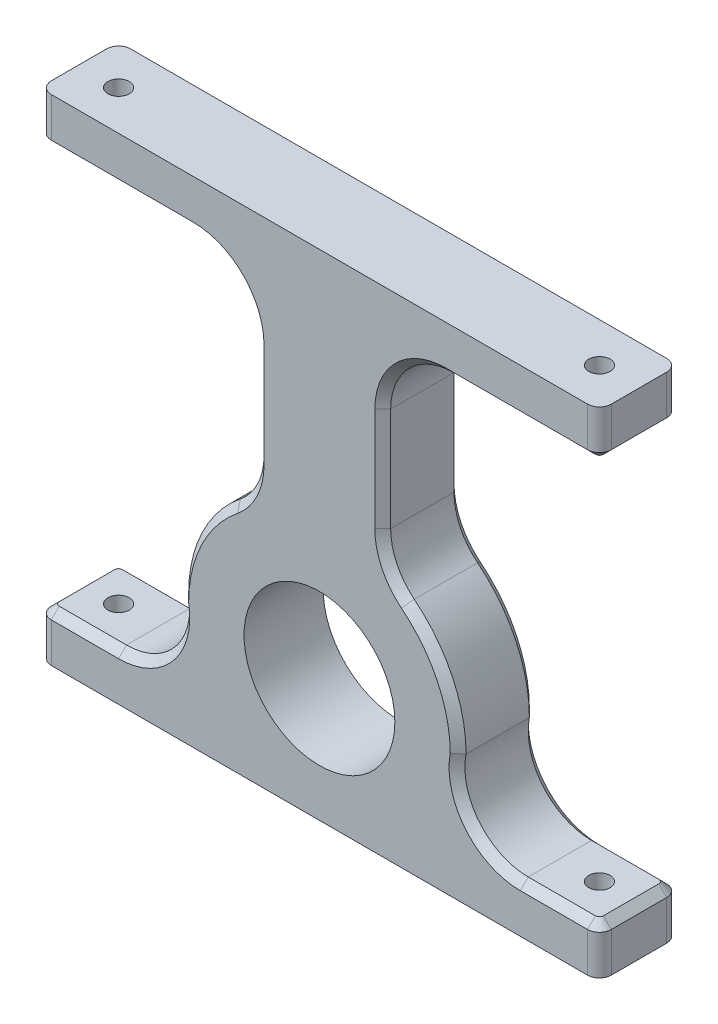
SolidWorks part; units mm, degrees
material "Nylon 101"
ref_plane "Front Plane" through (0, 0, 0) normal (0, 0, 1) x (1, 0, 0)
ref_plane "Top Plane" through (0, 0, 0) normal (0, 1, 0) x (1, 0, 0)
ref_plane "Right Plane" through (0, 0, 0) normal (1, 0, 0) x (0, 0, -1)
sketch "Sketch1" plane through (0, 0, 0) normal (0, 0, 1) x (1, 0, 0)
  line L0 (0, -19.0627) -> (50.7668, -19.0627) construction
  line L1 (50.7668, -19.0627) -> (70.7668, -19.0627)
  line L2 (70.7668, -19.0627) -> (70.7668, -31.0627)
  line L3 (70.7668, -31.0627) -> (-70.7668, -31.0627)
  line L4 (-70.7668, -31.0627) -> (-70.7668, -19.0627)
  line L5 (-70.7668, -19.0627) -> (-50.7668, -19.0627)
  line L6 (0, 19.0627) -> (0, 31.1992) construction
  line L7 (0, 31.1992) -> (16, 31.1992) construction
  line L9 (32, 81.9373) -> (70.7668, 81.9373)
  line L10 (70.7668, 81.9373) -> (70.7668, 93.9373)
  line L11 (70.7668, 93.9373) -> (-70.7668, 93.9373)
  line L12 (-70.7668, 93.9373) -> (-70.7668, 81.9373)
  line L13 (-70.7668, 81.9373) -> (-32, 81.9373)
  line L14 (0, 31.1992) -> (-16, 31.1992) construction
  line L16 (16, 31.1992) -> (16, 65.9373)
  line L17 (-16, 31.1992) -> (-16, 65.9373)
  line L18 (-32, 81.9373) -> (-16, 81.9373) construction
  line L19 (-16, 81.9373) -> (-16, 65.9373) construction
  line L20 (-70.7668, -19.0627) -> (-70.7668, 81.9373) construction
  line L21 (0, -19.0627) -> (70.7668, -19.0627) construction
  circle A0 centre (0, 0) radius 19.0627
  arc A1 (-16, 31.1992) -> (-35.0627, 0) centre (0, 0) ccw
  arc A2 (-50.7668, -19.0627) -> (-35.0627, 0) centre (-50.7668, -3.0627) ccw
  arc A3 (50.7668, -19.0627) -> (35.0627, 0) centre (50.7668, -3.0627) cw
  arc A4 (35.0627, 0) -> (16, 31.1992) centre (0, 0) ccw
  arc A5 (-16, 65.9373) -> (-32, 81.9373) centre (-32, 65.9373) ccw
  arc A6 (16, 65.9373) -> (32, 81.9373) centre (32, 65.9373) cw
  dimension "D2" = 16
  dimension "D5" = 16
  dimension "D6" = 16
  dimension "D11" = 16
  dimension "D12" = 125
  dimension "D16" = 38.1254
  dimension "D3" = 12
  dimension "D4" = 12
  dimension "D7" = 20
  dimension "D8" = 20
  dimension "D9" = 32
  dimension "D10" = 16
  dimension "D13" = 16
  dimension "D14" = 16
  dimension "D15" = 16
extrude "Boss-Extrude1" add sketch "Sketch1" along normal blind 20
sketch "Sketch2" plane through (0, -19.0627, 0) normal (0, 1, 0) x (1, 0, 0)
  line L0 (-50.7668, -10) -> (-60.7668, -10) construction
  line L1 (-50.7668, -20) -> (-50.7668, 0) construction
  circle A0 centre (-60.7668, -10) radius 2.7
  dimension "D2" = 5.4
  dimension "D1" = 10
extrude "Cut-Extrude1" cut sketch "Sketch2" against normal through all both and the other way through all
mirror "Mirror1" about plane through (0, 0, 0) normal (1, 0, 0) of "Cut-Extrude1"
fillet "Fillet1" radius 16 2 edges at (-16, 31.1992, 10) (16, 31.1992, 10)
fillet "Fillet4" radius 3 8 edges at (-70.7668, -25.0627, 0) (-70.7668, -25.0627, 20) (70.7668, -25.0627, 0) (70.7668, -25.0627, 20) (-70.7668, 87.9373, 0) (-70.7668, 87.9373, 20) (70.7668, 87.9373, 0) (70.7668, 87.9373, 20)
chamfer "Chamfer1" distance 2 angle 45 40 edges at (-31.6214, 15.1485, 20) (-17.5703, 32.8793, 20) (-16, 52.8646, 20) (-20.6863, 77.251, 20) (-49.8834, 81.9373, 20) (-69.8882, 81.9373, 19.1213) (-70.7668, 81.9373, 10) (-69.8882, 81.9373, 0.8787) (-49.8834, 81.9373, 0) (-31.6214, 15.1485, 0) (-20.6863, 77.251, 0) (-17.5703, 32.8793, 0) (-16, 52.8646, 0) (-38.4177, -13.2361, 20) (-59.2668, -19.0627, 20) (-69.8882, -19.0627, 19.1213) (-70.7668, -19.0627, 10) (-38.4177, -13.2361, 0) (-69.8882, -19.0627, 0.8787) (-59.2668, -19.0627, 0) (38.4177, -13.2361, 20) (59.2668, -19.0627, 20) (69.8882, -19.0627, 19.1213) (70.7668, -19.0627, 10) (69.8882, -19.0627, 0.8787) (38.4177, -13.2361, 0) (59.2668, -19.0627, 0) (31.6214, 15.1485, 20) (17.5703, 32.8793, 20) (16, 52.8646, 20) (20.6863, 77.251, 20) (49.8834, 81.9373, 20) (69.8882, 81.9373, 19.1213) (70.7668, 81.9373, 10) (69.8882, 81.9373, 0.8787) (31.6214, 15.1485, 0) (49.8834, 81.9373, 0) (17.5703, 32.8793, 0) (20.6863, 77.251, 0) (16, 52.8646, 0)
